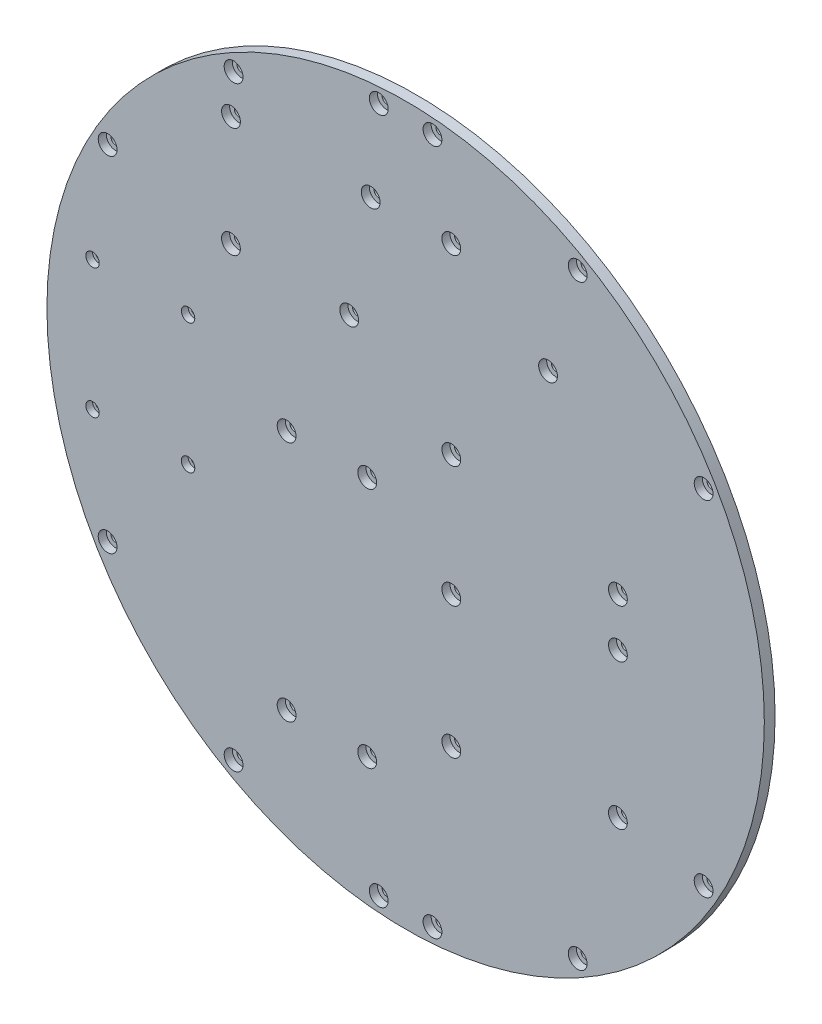
SolidWorks part; units mm, degrees
ref_plane "Plan de face" through (0, 0, 0) normal (0, 0, 1) x (1, 0, 0)
ref_plane "Plan de dessus" through (0, 0, 0) normal (0, 1, 0) x (1, 0, 0)
ref_plane "Plan de droite" through (0, 0, 0) normal (1, 0, 0) x (0, 0, -1)
sketch "Esquisse1" plane through (0, 0, 0) normal (0, 0, 1) x (1, 0, 0)
  line L0 (0, 0) -> (0, -128.06) construction
  line L1 (10, -127.669) -> (-10, -127.669) construction
  line L2 (0, 0) -> (0, 128.06) construction
  line L3 (10, 127.669) -> (-10, 127.669) construction
  line L4 (-64.03, -110.9032) -> (64.03, 110.9032) construction
  line L5 (110.9032, 64.03) -> (-110.9032, -64.03) construction
  line L6 (-64.03, 110.9032) -> (64.03, -110.9032) construction
  line L7 (-110.9032, 64.03) -> (110.9032, -64.03) construction
  circle A0 centre (0, 0) radius 133.5
  circle A1 centre (10, -127.669) radius 1.75
  circle A2 centre (-10, -127.669) radius 1.75
  circle A3 centre (0, 0) radius 128.06 construction
  circle A4 centre (10, 127.669) radius 1.75
  circle A5 centre (-10, 127.669) radius 1.75
  circle A6 centre (64.03, 110.9032) radius 1.75
  circle A7 centre (110.9032, 64.03) radius 1.75
  circle A8 centre (110.9032, -64.03) radius 1.75
  circle A9 centre (64.03, -110.9032) radius 1.75
  circle A10 centre (-64.03, -110.9032) radius 1.75
  circle A11 centre (-110.9032, -64.03) radius 1.75
  circle A12 centre (-110.9032, 64.03) radius 1.75
  circle A13 centre (-64.03, 110.9032) radius 1.75
  point P7 (0, -127.669)
  point P14 (0, 127.669)
  point P17 (0, 0)
  point P18 (0, 0)
  point P23 (0, 0)
  point P26 (0, 0)
  dimension "D1" = 256.12
  dimension "D3" = 3.5
  dimension "D8" = 267
  dimension "D2" = 20
  dimension "D4" = 30
  dimension "D5" = 30
  dimension "D6" = 30
  dimension "D7" = 30
extrude "Boss.-Extru.1" add sketch "Esquisse1" along normal blind 4
sketch "Esquisse2" plane through (0, 0, 4) normal (0, 0, 1) x (1, 0, 0)
  circle A0 centre (64.03, -110.9032) radius 3.5
  circle A1 centre (110.9032, -64.03) radius 3.5
  circle A2 centre (110.9032, 64.03) radius 3.5
  circle A3 centre (64.03, 110.9032) radius 3.5
  circle A4 centre (10, 127.669) radius 3.5
  circle A5 centre (-10, 127.669) radius 3.5
  circle A6 centre (-64.03, 110.9032) radius 3.5
  circle A7 centre (-110.9032, 64.03) radius 3.5
  circle A8 centre (-110.9032, -64.03) radius 3.5
  circle A9 centre (-64.03, -110.9032) radius 3.5
  circle A10 centre (-10, -127.669) radius 3.5
  circle A11 centre (10, -127.669) radius 3.5
  dimension "D1" = 7
extrude "Enlèv. mat.-Extru.1" cut sketch "Esquisse2" against normal blind 3
sketch "Esquisse3" plane through (0, 0, 4) normal (0, 0, 1) x (1, 0, 0)
  line L0 (-116.5279, -24.13) -> (-116.5279, 24.13) construction
  line L1 (-116.5279, 24.13) -> (-80.9679, 24.13) construction
  line L2 (-80.9679, 24.13) -> (-80.9679, -24.13) construction
  line L3 (-80.9679, -24.13) -> (-116.5279, -24.13) construction
  circle A0 centre (0, 0) radius 119 construction
  circle A3 centre (-116.5279, -24.13) radius 1.25
  circle A4 centre (-116.5279, 24.13) radius 1.25
  circle A5 centre (-80.9679, 24.13) radius 1.25
  circle A6 centre (-80.9679, -24.13) radius 1.25
  dimension "D1" = 238
  dimension "D2" = 35.56
  dimension "D4" = 2.5
  dimension "D3" = 48.26
extrude "Enlèv. mat.-Extru.2" cut sketch "Esquisse3" against normal up to next
sketch "Esquisse4" plane through (0, 0, 4) normal (0, 0, 1) x (1, 0, 0)
  circle A0 centre (-116.5279, -24.13) radius 2.5
  circle A1 centre (-116.5279, 24.13) radius 2.5
  circle A2 centre (-80.9679, 24.13) radius 2.5
  circle A3 centre (-80.9679, -24.13) radius 2.5
  dimension "D1" = 5
extrude "Enlèv. mat.-Extru.3" cut sketch "Esquisse4" against normal blind 2.5
sketch "Esquisse5" plane through (0, 0, 4) normal (0, 0, 1) x (1, 0, 0)
  circle A0 centre (-44.3, -85) radius 1.75
  circle A1 centre (-44.3, 5) radius 1.75
  circle A2 centre (-14.3, 5) radius 1.75
  circle A3 centre (-14.3, -85) radius 1.75
  circle A5 centre (0, 0) radius 133.5
  circle A6 centre (0, 0) radius 133.5 construction
  dimension "D4" = 3.5
  dimension "D1" = 90
  dimension "D2" = 30
  dimension "D3" = 5
  dimension "D6" = 14.3
  dimension "D5" = 0
extrude "Enlèv. mat.-Extru.4" cut sketch "Esquisse5" against normal up to next
sketch "Esquisse6" plane through (0, 0, 4) normal (0, 0, 1) x (1, 0, 0)
  circle A0 centre (-44.3, -85) radius 3.5
  circle A1 centre (-14.3, -85) radius 3.5
  circle A2 centre (-44.3, 5) radius 3.5
  circle A3 centre (-14.3, 5) radius 3.5
  dimension "D1" = 7
extrude "Enlèv. mat.-Extru.5" cut sketch "Esquisse6" against normal blind 3
sketch "Esquisse7" plane through (0, 0, 4) normal (0, 0, 1) x (1, 0, 0)
  circle A0 centre (-65, 55) radius 1.75
  circle A1 centre (-65, 96) radius 1.75
  circle A2 centre (-21, 54) radius 1.75
  circle A3 centre (-13, 96) radius 1.75
  circle A4 centre (-44.3, 5) radius 3.5 construction
  circle A6 centre (-14.3, 5) radius 3.5 construction
  dimension "D5" = 3.5
  dimension "D7" = 6.7
  dimension "D1" = 44
  dimension "D2" = 41
  dimension "D3" = 42
  dimension "D4" = 52
  dimension "D6" = 50
extrude "Enlèv. mat.-Extru.6" cut sketch "Esquisse7" against normal up to next
sketch "Esquisse8" plane through (0, 0, 4) normal (0, 0, 1) x (1, 0, 0)
  circle A0 centre (-65, 55) radius 3.5
  circle A1 centre (-65, 96) radius 3.5
  circle A2 centre (-21, 54) radius 3.5
  circle A3 centre (-13, 96) radius 3.5
  dimension "D1" = 7
extrude "Enlèv. mat.-Extru.7" cut sketch "Esquisse8" against normal blind 3
sketch "Esquisse9" plane through (0, 0, 0) normal (0, 0, -1) x (-1, 0, 0)
  circle A0 centre (-17, 96) radius 1.75
  circle A1 centre (-17, 28) radius 1.75
  circle A2 centre (-53, 73) radius 1.75
  circle A3 centre (-79, 14) radius 1.75
  circle A4 centre (13, 96) radius 1.75 construction
  circle A5 centre (13, 96) radius 1.75 construction
  dimension "D1" = 3.5
  dimension "D2" = 68
  dimension "D3" = 23
  dimension "D4" = 36
  dimension "D5" = 62
  dimension "D6" = 30
  dimension "D7" = 82
extrude "Enlèv. mat.-Extru.8" cut sketch "Esquisse9" against normal up to next
sketch "Esquisse10" plane through (0, 0, 4) normal (0, 0, 1) x (1, 0, 0)
  circle A0 centre (17, 28) radius 3.5
  circle A1 centre (17, 96) radius 3.5
  circle A2 centre (53, 73) radius 3.5
  circle A3 centre (79, 14) radius 3.5
  dimension "D1" = 7
extrude "Enlèv. mat.-Extru.9" cut sketch "Esquisse10" against normal blind 3
sketch "Esquisse11" plane through (0, 0, 0) normal (0, 0, -1) x (-1, 0, 0)
  circle A0 centre (-17, -17) radius 1.75
  circle A1 centre (-17, -66) radius 1.75
  circle A2 centre (-79, -4) radius 1.75
  circle A3 centre (-79, -58) radius 1.75
  circle A4 centre (-17, 28) radius 1.75 construction
  circle A5 centre (-17, 28) radius 1.75 construction
  circle A6 centre (-79, 14) radius 1.75 construction
  dimension "D1" = 3.5
  dimension "D2" = 49
  dimension "D6" = 18
  dimension "D3" = 62
  dimension "D4" = 13
  dimension "D5" = 54
extrude "Enlèv. mat.-Extru.10" cut sketch "Esquisse11" against normal up to next
sketch "Esquisse12" plane through (0, 0, 4) normal (0, 0, 1) x (1, 0, 0)
  circle A0 centre (17, -66) radius 3.5
  circle A1 centre (17, -17) radius 3.5
  circle A2 centre (79, -4) radius 3.5
  circle A3 centre (79, -58) radius 3.5
  dimension "D1" = 7
extrude "Enlèv. mat.-Extru.11" cut sketch "Esquisse12" against normal blind 3
